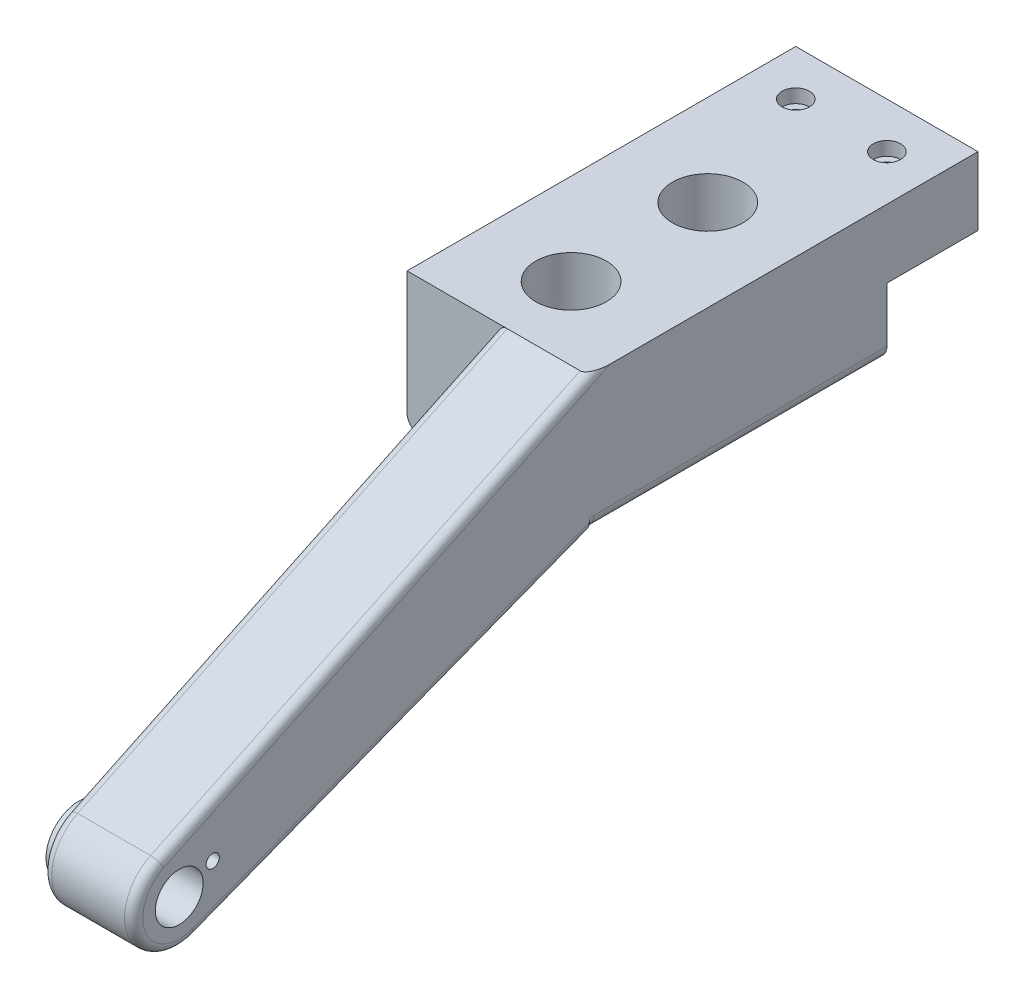
SolidWorks part; units mm, degrees
ref_plane "Front Plane" through (0, 0, 0) normal (0, 0, 1) x (1, 0, 0)
ref_plane "Top Plane" through (0, 0, 0) normal (0, 1, 0) x (1, 0, 0)
ref_plane "Right Plane" through (0, 0, 0) normal (1, 0, 0) x (0, 0, -1)
sketch "Sketch1" plane through (0, 0, 0) normal (0, 1, 0) x (1, 0, 0)
  line L1 (-20, 75) -> (20, 75)
  line L3 (-20, -75) -> (20, -75)
  line L4 (20, -75) -> (20, 75)
  line L5 (-20, -75) -> (-20, 75)
  circle A0 centre (0, -61.1649) radius 7.5
  circle A1 centre (0, -31.1649) radius 7.5
extrude "Boss-Extrude1" add sketch "Sketch1" against normal blind 30 contours L5 L1 L4 L3
sketch "Sketch3" plane through (0, 0, 0) normal (0, 1, 0) x (1, 0, 0)
  circle A0 centre (0, -60) radius 7.5
  circle A1 centre (0, -30) radius 7.5
extrude "Cut-Extrude1" cut sketch "Sketch3" against normal blind 30 contours A0 | A1
sketch "Sketch4" plane through (-20, 0, 0) normal (-1, 0, 0) x (0, 0, 1)
  line L1 (-75, -30) -> (-75, 0) construction
  line L2 (-75, -8) -> (0, -30)
  line L3 (75, -30) -> (-75, -30) construction
  line L4 (0, -30) -> (-75, -30)
  line L5 (-75, -30) -> (-75, -8)
extrude "Cut-Extrude2" cut sketch "Sketch4" against normal blind 49
sketch "Sketch6" plane through (0, 0, -75) normal (0, 0, -1) x (-1, 0, 0)
  line L1 (-20, 0) -> (20, 0)
  line L2 (-20, 0) -> (-20, -30)
  line L3 (-20, -30) -> (20, -30)
  line L4 (20, 0) -> (20, -30)
extrude "Boss-Extrude2" add sketch "Sketch6" along normal blind 50 and the other way blind 87
sketch "Sketch7" plane through (-20, 0, 0) normal (-1, 0, 0) x (0, 0, 1)
  line L1 (-125, -30) -> (-125, 0) construction
  line L2 (-125, -10) -> (-25, -30)
  line L3 (75, -30) -> (-125, -30) construction
  line L4 (-25, -30) -> (-125, -30)
  line L5 (-125, -30) -> (-125, -10)
extrude "Cut-Extrude3" cut sketch "Sketch7" against normal blind 50
sketch "Sketch8" plane through (0, 0, 75) normal (0, 0, 1) x (1, 0, 0)
  line L10 (20, -30) -> (6, -30)
  line L11 (-20, -30) -> (20, -30) construction
  line L12 (6, -30) -> (6, 0)
  line L13 (-20, 0) -> (20, 0) construction
  line L14 (6, 0) -> (20, 0)
  line L15 (20, 0) -> (20, -30)
  line L16 (-20, -30) -> (-6, -30)
  line L17 (-6, -30) -> (-6, 0)
  line L18 (-6, 0) -> (-20, 0)
  line L19 (-20, -30) -> (-20, 0) construction
  line L20 (-20, 0) -> (-20, -30)
extrude "Boss-Extrude4" add sketch "Sketch8" along normal blind 50
sketch "Sketch11" plane through (0, 0, 0) normal (0, 1, 0) x (1, 0, 0)
  line L0 (6, -75) -> (20, -75)
  line L1 (20, -125) -> (20, 125) construction
  line L2 (20, -75) -> (20, -125)
  line L3 (20, -125) -> (6, -125)
  line L4 (6, -125) -> (6, -75)
  line L5 (-6, -75) -> (-6, -125)
  line L6 (-6, -125) -> (-20, -125)
  line L7 (-20, -125) -> (-20, -75)
  line L8 (-20, -125) -> (-20, 125) construction
  line L9 (-20, -75) -> (-6, -75)
extrude "Cut-Extrude4" cut sketch "Sketch11" against normal blind 15
sketch "Sketch12" plane through (0, 0, 125) normal (0, 0, 1) x (1, 0, 0)
  line L1 (-20, -15) -> (-6, -15)
  line L2 (-20, -15) -> (-20, -30)
  line L3 (-20, -30) -> (-6, -30)
  line L4 (-6, -15) -> (-6, -30)
  line L5 (6, -15) -> (20, -15)
  line L6 (6, -15) -> (6, -30)
  line L7 (6, -30) -> (20, -30)
  line L8 (20, -15) -> (20, -30)
extrude "Boss-Extrude5" add sketch "Sketch12" along normal blind 10
sketch "Sketch13" plane through (-6, 0, 0) normal (1, 0, 0) x (0, 0, -1)
  circle A0 centre (-125, -22.5) radius 5
extrude "Boss-Extrude6" add sketch "Sketch13" along normal up to surface (12 mm away) contours A0 up to face at (6, -22.5, 105)
sketch "Sketch14" plane through (0, -30, 0) normal (0, -1, 0) x (1, 0, 0)
  circle A0 centre (0, 60) radius 7.5
  circle A1 centre (0, 60) radius 6
  circle A2 centre (0, 30) radius 6
  circle A3 centre (0, 30) radius 7.5
extrude "Boss-Extrude7" add sketch "Sketch14" against normal blind 5
sketch "Sketch15" plane through (20, 0, 0) normal (1, 0, 0) x (0, 0, -1)
  line L0 (125, 0) -> (105, 0)
  line L1 (-75, 0) -> (125, 0) construction
  circle A0 centre (52.5, 373.9316) radius 377.5991
extrude "Cut-Extrude5" cut sketch "Sketch15" against normal blind 50 contours A0
fillet "Fillet1" radius 3 2 edges at (20, -30, 55) (-20, -30, 55)
fillet "Fillet2" radius 3 8 edges at (-20, -18.5, -82.5) (-19.1213, -29.1213, -29.3934) (0, -30, -25) (19.1213, -29.1213, -29.3934) (-20, -5, -125) (20, -5, -125) (0, -10, -125) (20, -18.5, -82.5)
sketch "Sketch17" plane through (0, 0, 75) normal (0, 0, 1) x (1, 0, 0)
  line L0 (20, 0) -> (20, -30)
  line L1 (14.0365, -30) -> (20, -30)
  line L2 (6, -30) -> (17, -30) construction
  line L3 (20, 0) -> (-20, 0)
  line L4 (-20, 0) -> (-20, -30)
  line L5 (-20, -30) -> (14.0365, -30)
extrude "Boss-Extrude11" add sketch "Sketch17" along normal up to surface (60 mm away) up to face at (13.9243, -23.5243, 135)
sketch "Sketch23" plane through (0, 0, 135) normal (0, 0, 1) x (1, 0, 0)
  line L0 (-20, -15) -> (0, -15)
  line L1 (-20, 0) -> (-20, -30) construction
  line L3 (0, -30) -> (0, -15)
  line L4 (-20, -30) -> (20, -30) construction
  line L6 (-20, -30) -> (0, -30)
  line L7 (-20, -15) -> (-20, -30)
  line L9 (-20, -30) -> (20, -30)
  line L10 (-20, -30) -> (-20, 0)
  line L11 (-20, 0) -> (20, 0)
  line L12 (20, -30) -> (20, 0)
  line M1 (-20, 0) -> (-20, -30)
  line M2 (-20, -30) -> (20, -30)
  line M3 (20, -30) -> (20, 0)
  line M4 (20, 0) -> (-20, 0)
extrude "Cut-Extrude8" cut sketch "Sketch23" against normal up to surface (60 mm away) contours L3 L0 M2 M3 M4 M1 region at (3.3333, -12.5, 135) up to face at (19.2071, -29.2071, 75)
sketch "Sketch25" plane through (0, 0, 75) normal (0, 0, 1) x (1, 0, 0)
  line L0 (-20, -15) -> (-20, 0)
  line L1 (-20, 0) -> (0, 0)
  line L2 (-20, 0) -> (20, 0) construction
  line L3 (0, 0) -> (0, -15)
  line L4 (0, -15) -> (-20, -15)
extrude "Boss-Extrude13" add sketch "Sketch25" along normal up to surface (60 mm away) up to face at (-10, -22.5, 135)
sketch "Sketch26" plane through (0, 0, 0) normal (1, 0, 0) x (0, 0, -1)
  circle A0 centre (-125, -15) radius 5
extrude "Boss-Extrude14" add sketch "Sketch26" along normal up to surface (20 mm away) up to face at (20, -9.3154, -31.9576)
sketch "Sketch27" plane through (0, 0, 75) normal (0, 0, 1) x (1, 0, 0)
  line L1 (20, 0) -> (-20, 0)
  line L2 (20, 0) -> (20, -60)
  line L3 (20, -60) -> (-20, -60)
  line L4 (-20, 0) -> (-20, -60)
extrude "Boss-Extrude15" add sketch "Sketch27" along normal up to surface (60 mm away) up to face at (-10, -15, 135)
sketch "Sketch28" plane through (0, 0, 75) normal (0, 0, -1) x (-1, 0, 0)
  line L0 (20, -27) -> (20, -60) construction
  line L1 (-20, -60) -> (20, -60)
  line L2 (-20, -60) -> (-20, -30)
  line L3 (-20, -30) -> (20, -30)
  line L4 (20, -60) -> (20, -30)
extrude "Cut-Extrude9" cut sketch "Sketch28" against normal blind 1
sketch "Sketch29" plane through (0, 0, 135) normal (0, 0, 1) x (1, 0, 0)
  line L0 (20, 0) -> (-20, 0) construction
  line L1 (20, -60) -> (0, -60)
  line L2 (20, -60) -> (20, 0)
  line L3 (20, 0) -> (0, 0)
  line L4 (0, -60) -> (0, 0)
extrude "Cut-Extrude10" cut sketch "Sketch29" against normal up to surface (59 mm away) up to face at (0, -45, 76)
fillet "Fillet6" radius 3 1 edges at (-20, -30, 75.5)
fillet "Fillet7" radius 3 1 edges at (20, -30, 75.5)
sketch "Sketch30" plane through (0, 0, 135) normal (0, 0, 1) x (1, 0, 0)
  line L0 (-20, 0) -> (-20, -30)
  line L1 (-20, 0) -> (-20, -60) construction
  line L2 (-20, -15) -> (0, -15)
  line L3 (0, 0) -> (0, -60) construction
  line L4 (0, -15) -> (0, 0)
  line L5 (0, 0) -> (-20, 0)
  line M1 (0, -60) -> (0, 0)
  line M2 (0, 0) -> (-20, 0)
  line M3 (-20, 0) -> (-20, -60)
extrude "Cut-Extrude11" cut sketch "Sketch30" against normal up to surface (59 mm away) contours L2 M3 M1 M2 region at (-10, -7.5, 135) up to face at (11.5243, -17.5243, 76)
sketch "Sketch31" plane through (0, 0, 0) normal (1, 0, 0) x (0, 0, -1)
  line L0 (-129.7694, -41.2162) -> (-129.0122, -40.847)
  line L1 (-76, -15) -> (-76, -30)
  line L2 (-76, -30) -> (-118.7075, -57.7744)
  line L3 (-129.6113, -41.0081) -> (-129.7694, -41.2162)
  line L4 (-89.6197, -15) -> (-129.6113, -41.0081)
  line L5 (-76, -30) -> (-76, -60)
  line L6 (-76, -60) -> (-135, -60)
  line L7 (-135, -60) -> (-135, -15)
  line L8 (-135, -15) -> (-76, -15)
  line L9 (-96, -19.1494) -> (-129.6113, -41.0081) construction
  line L10 (-96, -15) -> (-96, -19.1494) construction
  circle A0 centre (-125.0122, -50.0122) radius 10
  line M9 (-76, -15) -> (-135, -15)
  line M10 (-135, -15) -> (-135, -60)
  line M11 (-135, -60) -> (-76, -60)
  line M12 (-76, -60) -> (-76, -30)
  dimension "D1" = 20
extrude "Cut-Extrude13" cut sketch "Sketch31" against normal blind 28 contours A0 M10 M11 | A0 L2 M11 M12 | A0 L3 L4 M9 M10 region at (0, -24.9817, 119.9741) region at (0, -57.7806, 132.7806) region at (0, -50.0084, 91.4032)
sketch "Sketch32" plane through (0, 0, 0) normal (1, 0, 0) x (0, 0, -1)
  line L0 (-76, -30) -> (-76, 0)
  line L1 (-76, 0) -> (-129.7694, -41.2162)
  line L2 (-129.7694, -41.2162) -> (-76, -30)
extrude "Boss-Extrude16" add sketch "Sketch32" against normal up to surface (20 mm away) up to face at (-20, -28.5466, 55.3206)
sketch "Sketch33" plane through (0, 0, 0) normal (1, 0, 0) x (0, 0, -1)
  circle A0 centre (-125.0122, -50.0122) radius 5
extrude "Boss-Extrude17" add sketch "Sketch33" along normal up to surface (20 mm away) contours A0 up to face at (20, -11.526, -18.3379)
ref_plane "Plane2" through (0, 10, 0) normal (0, 1, 0) x (1, 0, 0)
sketch "Sketch34" plane through (0, 0, 0) normal (1, 0, 0) x (0, 0, -1)
  line L0 (-129.6113, -41.0081) -> (-129.7694, -41.2162)
  line L1 (-129.6113, -41.0081) -> (-76, 0)
  line L2 (-76, 0) -> (-76, -30)
  line L3 (-76, -30) -> (-76, 0) construction
  line L4 (-76, -30) -> (-118.7075, -57.7744)
  arc A0 (-129.7694, -41.2162) -> (-118.7075, -57.7744) centre (-125.0122, -50.0122) ccw
extrude "Cut-Extrude15" cut sketch "Sketch34" against normal up to surface (20 mm away) up to face at (-20, -30.8448, 56.4126)
extrude "Cut-Extrude16" cut sketch "Sketch34<2>" along normal up to surface (20 mm away) up to face at (20, -11.526, -18.3379)
sketch "Sketch34<2>" plane through (0, 0, 0) normal (1, 0, 0) x (0, 0, -1) same geometry as "Sketch34"
extrude "Boss-Extrude19" add sketch "Sketch34<3>" along normal up to surface (20 mm away) up to face at (20, -11.526, -18.3379)
sketch "Sketch34<3>" plane through (0, 0, 0) normal (1, 0, 0) x (0, 0, -1) same geometry as "Sketch34"
sketch "Sketch38" plane through (0, 0, 0) normal (-1, 0, 0) x (0, 0, 1)
  circle A0 centre (125.0122, -50.0122) radius 5
sketch "Sketch39" plane through (0, 0, 0) normal (-1, 0, 0) x (0, 0, 1)
  line L0 (162.0273, -59.1835) -> (76, -78.9424)
  line L1 (169.997, -40.8408) -> (76, 0)
  line L2 (76, -30) -> (76, 0) construction
  line L3 (76, 0) -> (129.6113, -41.0081) construction
  line L4 (76, 0) -> (76, -30)
  line L6 (162.0273, -59.1835) -> (76, -30)
  line L7 (76, -78.9424) -> (76, -30)
  arc A0 (162.0273, -59.1835) -> (169.997, -40.8408) centre (166.0122, -50.0122) ccw
  line M6 (129.6113, -41.0081) -> (76, 0)
  line M8 (76, -30) -> (118.7075, -57.7744)
  arc M9 (118.7075, -57.7744) -> (129.7694, -41.2162) centre (125.0122, -50.0122) ccw
  line M10 (129.7694, -41.2162) -> (129.6113, -41.0081)
extrude "Cut-Extrude17" cut sketch "Sketch39" against normal blind 23 contours L7 L0 L6 M9 M8 | L6 M9 M8 region at (0, -58.461, 102.3812) region at (0, -47.5284, 112.7515)
extrude "Boss-Extrude21" add sketch "Sketch39<3>" against normal blind 20 contours L6 A0 L1 M6 M10 M9 region at (0, -36.3816, 138.4753)
sketch "Sketch39<3>" plane through (0, 0, 0) normal (-1, 0, 0) x (0, 0, 1) same geometry as "Sketch39"
sketch "Sketch40" plane through (0, -4.0074, 0) normal (-1, 0, 0) x (0, 0, 1)
  circle A0 centre (166.0122, -50.0122) radius 4.5
extrude "Boss-Extrude22" add sketch "Sketch40" along normal up to surface (12 mm away)
ref_plane "Plane5" through (0, 0, 0) normal (-1, 0, 0) x (0, 0, 1)
sketch "Sketch42" plane through (0, 0, 0) normal (-1, 0, 0) x (0, 0, 1)
  line L0 (166.0122, -54.0196) -> (166.0122, -54.0122)
  line L1 (170.3172, -44.9863) -> (76, 0)
  line L2 (76, 0) -> (76, -30)
  line L3 (162.4124, -63.3418) -> (76, -30)
  line L4 (175.8593, -55.7544) -> (179.2704, -36.4741)
  line L5 (179.2704, -36.4741) -> (76, 0)
  circle A0 centre (166.0122, -54.0122) radius 10
extrude "Cut-Extrude18" cut sketch "Sketch42" against normal blind 20 contours A0 L4 L5 L1 region at (0, -28.5967, 144.6768)
extrude "Boss-Extrude23" add sketch "Sketch42<4>" against normal blind 20 contours A0 L1 L2 L3 | A0 region at (0, -31.8969, 115.5317) region at (0, -48.8269, 174.2302)
sketch "Sketch42<4>" plane through (0, 0, 0) normal (-1, 0, 0) x (0, 0, 1) same geometry as "Sketch42"
fillet "Fillet8" radius 2 6 edges at (20, -46.6709, 119.2062) (20, -57.9675, 175.1967) (0, -46.6709, 119.2062) (0, -57.9675, 175.1967) (20, -22.4932, 123.1586) (0, -22.4932, 123.1586)
sketch "Sketch44" plane through (20, 0, 0) normal (1, 0, 0) x (0, 0, -1)
  line L0 (0, 0) -> (105, 0)
  line L1 (105, 0) -> (105, -4.5055)
  line L2 (105, -4.5055) -> (0, -4.5055)
  line L3 (0, -4.5055) -> (0, 0)
extrude "Boss-Extrude25" add sketch "Sketch44" against normal up to surface (40 mm away) up to face at (-20, -11.526, -18.3379)
sketch "Sketch46" plane through (20, 0, 0) normal (1, 0, 0) x (0, 0, -1)
  line L0 (-71.3543, 0) -> (122, 0) construction
  line L1 (25.3229, 0) -> (-14.6771, 0)
  line L2 (25.3229, 0) -> (25.3229, -6)
  line L3 (25.3229, -27) -> (-14.6771, -27)
  line L4 (-14.6771, 0) -> (-14.6771, -27)
  line L5 (-75, -27) -> (24.7029, -27) construction
  line L6 (63.8734, -19.1659) -> (62.5127, -12.362)
  line L7 (24.7029, -27) -> (122, -7.5406) construction
  line L8 (19.3229, -6) -> (-8.6771, -6)
  line L9 (-8.6771, -6) -> (-8.6771, -21)
  line L10 (19.3229, -21) -> (-8.6771, -21)
  line L12 (19.3229, -21) -> (94.3229, -6)
  line L13 (19.3229, -6) -> (103.4664, -6)
  line L14 (25.3229, -19.8) -> (25.3229, -27)
  line L15 (19.3229, -6) -> (19.3229, -21) construction
  line L16 (25.3229, 0) -> (25.3229, -27) construction
  dimension "D1" = 6
extrude "Cut-Extrude20" cut sketch "Sketch46" against normal blind 59 and the other way through all contours L13 L8 L9 L10 L12 region at (20, -12.0687, -27.6511)
fillet "Fillet10" radius 2 1 edges at (0, -6, -94.3229)
sketch "Sketch48" plane through (0, 0, 8.6771) normal (0, 0, -1) x (-1, 0, 0)
  line L0 (-20, -21) -> (20, -21)
  line L1 (-20, -21) -> (-20, -6)
  line L2 (20, -21) -> (20, -6)
  line L3 (-20, -6) -> (20, -6)
extrude "Boss-Extrude28" add sketch "Sketch48" along normal blind 28
sketch "Sketch49" plane through (20, 0, 0) normal (1, 0, 0) x (0, 0, -1)
  line L0 (19.3229, -6) -> (19.3229, 0)
  line L7 (-71.3543, 0) -> (122, 0) construction
  line L8 (19.3229, -6) -> (19.3229, -30)
  line L9 (19.3229, -30) -> (-20.6771, -30)
  line L10 (-20.6771, -30) -> (-20.6771, 0)
  line L11 (-20.6771, 0) -> (19.3229, 0)
  line L12 (-20.6771, -30) -> (-10.6771, -30)
  line L13 (-10.6771, -30) -> (-10.6771, -15)
  line L14 (-10.6771, -15) -> (9.3229, -15)
  line L15 (9.3229, -15) -> (9.3229, 0)
  line M5 (19.3229, -21) -> (19.3229, -6)
  line M9 (122, 0) -> (-71.3543, 0)
  line M15 (-75, -27) -> (24.7029, -27)
sketch "Sketch50" plane through (0, 0, 0) normal (0, 1, 0) x (1, 0, 0)
  line L0 (20, 9.3229) -> (-20, 9.3229)
  line L1 (-20, -76) -> (-20, 122) construction
  line L2 (-20, 9.3229) -> (-20, -0.6771)
  line L3 (-20, -0.6771) -> (-10, -0.6771)
  line L4 (-10, -0.6771) -> (10, -0.6771)
  circle A0 centre (10, -0.6771) radius 1.5
  circle A1 centre (-10, -0.6771) radius 1.5
extrude "Cut-Extrude21" cut sketch "Sketch49" against normal blind 49 contours L15 L14 L13 L8 L0 M15 M5 M9 | L13 L9 L8 M15 region at (20, -17.0294, -7.264) region at (20, -28.5, -4.3229)
sketch "Sketch51" plane through (0, 0, -19.3229) normal (0, 0, 1) x (1, 0, 0)
  line L1 (24.2973, -37.591) -> (-28.6622, -37.591)
  line L2 (24.2973, -37.591) -> (24.2973, 2.6321)
  line L3 (24.2973, 2.6321) -> (-28.6622, 2.6321)
  line L4 (-28.6622, -37.591) -> (-28.6622, 2.6321)
extrude "Cut-Extrude22" cut sketch "Sketch51" against normal blind 136
extrude "Cut-Extrude23" cut sketch "Sketch50" against normal blind 136 contours A0 | L3 A1 L4 | L4 A1 L3 region at (-10, 0, 0.0405) region at (10, 0, -0.7804) region at (-10, 0, 1.3138)
sketch "Sketch52" plane through (0, 0, 0) normal (0, 1, 0) x (1, 0, 0)
  circle A0 centre (10, -0.6771) radius 3
  circle A1 centre (-10, -0.6771) radius 3
  circle A2 centre (10, -0.6771) radius 1.5
  circle A3 centre (-10, -0.6771) radius 1.5
extrude "Cut-Extrude24" cut sketch "Sketch52" against normal blind 3
sketch "Sketch54" plane through (0, 0, 0) normal (0, 1, 0) x (1, 0, 0)
  circle A0 centre (0, -60) radius 7.75
  circle A1 centre (0, -30) radius 7.75
extrude "Cut-Extrude26" cut sketch "Sketch54" against normal up to surface (25 mm away) up to face at (0, -25, 54)
sketch "Sketch55" plane through (20, 0, 0) normal (1, 0, 0) x (0, 0, -1)
  circle A0 centre (-166.0122, -54.0122) radius 5.25
  circle A2 centre (-158.6646, -50.8479) radius 1.5
extrude "Cut-Extrude27" cut sketch "Sketch55" against normal blind 35 contours A0
sketch "Sketch56" plane through (20, 0, 0) normal (1, 0, 0) x (0, 0, -1)
  circle A1 centre (-158.6646, -50.8479) radius 1.45
extrude "Cut-Extrude28" cut sketch "Sketch56" against normal blind 10
sketch "Sketch58" plane through (0, 0, 0) normal (-1, 0, 0) x (0, 0, 1)
  circle A0 centre (166.0122, -54.0122) radius 5.25
  circle A1 centre (166.0122, -54.0122) radius 7.25
extrude "Boss-Extrude29" add sketch "Sketch58" along normal blind 2
